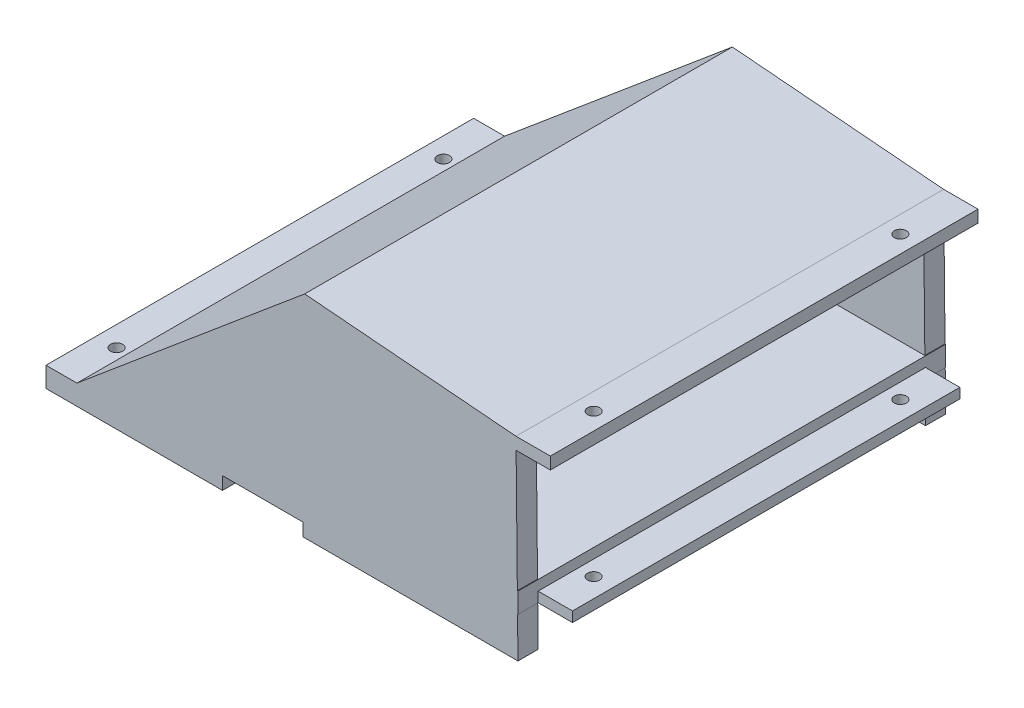
SolidWorks part; units mm, degrees
ref_plane "Front Plane" through (0, 0, 0) normal (0, 0, 1) x (1, 0, 0)
ref_plane "Top Plane" through (0, 0, 0) normal (0, 1, 0) x (1, 0, 0)
ref_plane "Right Plane" through (0, 0, 0) normal (1, 0, 0) x (0, 0, -1)
sketch "Sketch1" plane through (0, 0, 0) normal (0, 0, 1) x (1, 0, 0)
  line L2 (0, 0) -> (0, -6)
  line L6 (-234.6631, -86) -> (-250, -86)
  line L7 (-250, -86) -> (-250, -96)
  line L8 (-250, -96) -> (-230, -96)
  line L12 (-206.1649, -76) -> (0.9775, -76)
  line L16 (-16.0425, -66) -> (-118.6219, -66)
  line L20 (-16.0425, -66) -> (-16.0425, -71)
  line L21 (-16.0425, -71) -> (0.9775, -71)
  line L22 (0.9775, -71) -> (0.9775, -76)
  line L26 (0.9775, -66) -> (-92.0225, -66) construction
  line L27 (0.9775, -66) -> (0.9775, -13.5) construction
  line L28 (0.9775, -13.5) -> (-92.0225, -13.5) construction
  line L29 (-92.0225, -66) -> (-92.0225, -13.5) construction
  line L30 (-17.02, -6) -> (-118.6219, 2.463)
  line L31 (-118.6219, -1) -> (-99.8219, -1) construction
  line L32 (-118.6219, -1) -> (-118.6219, -66) construction
  line L33 (-118.6219, -66) -> (-99.8219, -66) construction
  line L34 (-99.8219, -1) -> (-99.8219, -66) construction
  line L39 (-17.02, -6) -> (0, -6)
  line L41 (-118.6219, 2.463) -> (-118.6219, -66)
  line L44 (-138.6219, -19.3246) -> (-138.6219, -66)
  line L45 (-138.6219, -66) -> (-194.2474, -66)
  line L46 (0, 0) -> (-17.02, 0)
  line L48 (-230, -96) -> (-206.1649, -76)
  line L49 (-17.02, 0) -> (-121.7736, 8.7256)
  line L50 (-234.6631, -86) -> (-121.7736, 8.7256)
  line L51 (-194.2474, -66) -> (-138.6219, -19.3246)
  point P13 (-250, -91)
  point P18 (0, -3)
  dimension "D1" = 250
  dimension "D2" = 20
  dimension "D3" = 20
  dimension "D4" = 10
  dimension "D5" = 5
  dimension "D6" = 6
  dimension "D7" = 20
  dimension "D8" = 5
  dimension "D9" = 65
  dimension "D10" = 52.5
  dimension "D11" = 40
  dimension "D12" = 93
  dimension "D13" = 18.8
  dimension "D14" = 65
  dimension "D18" = 17.02
extrude "Boss-Extrude1" add sketch "Sketch1" along normal blind 212
sketch "Sketch2" plane through (0, -76, 0) normal (0, -1, 0) x (1, 0, 0)
  line L1 (0.9775, 212) -> (-16.0425, 212)
  line L2 (0.9775, 212) -> (0.9775, 202)
  line L3 (0.9775, 202) -> (-16.0425, 202)
  line L4 (-16.0425, 212) -> (-16.0425, 202)
  line L5 (0.9775, 0) -> (-16.0425, 0)
  line L6 (0.9775, 0) -> (0.9775, 10)
  line L7 (0.9775, 10) -> (-16.0425, 10)
  line L8 (-16.0425, 0) -> (-16.0425, 10)
  dimension "D1" = 10
  dimension "D2" = 17.02
extrude "Cut-Extrude1" cut sketch "Sketch2" against normal up to next
sketch "Sketch3" plane through (-118.6219, 0, 0) normal (1, 0, 0) x (0, 0, -1)
  line L1 (-163.5, -0.037) -> (-48.5, -0.037) construction
  line L2 (-163.5, -0.037) -> (-163.5, -65.037) construction
  line L3 (-163.5, -65.037) -> (-48.5, -65.037) construction
  line L4 (-48.5, -0.037) -> (-48.5, -65.037) construction
  line L6 (-212, 2.463) -> (0, 2.463) construction
  line L7 (-212, -66) -> (-212, 2.463) construction
  line L8 (-106, -65.037) -> (-106, -6) construction
  circle A0 centre (-159.5, -12.537) radius 1.5
  circle A1 centre (-159.5, -52.537) radius 1.5
  circle A2 centre (-52.5, -52.537) radius 1.5
  circle A3 centre (-52.5, -12.537) radius 1.5
  dimension "D1" = 3
  dimension "D2" = 3
  dimension "D7" = 4
  dimension "D3" = 115
  dimension "D4" = 65
  dimension "D5" = 2.5
  dimension "D6" = 48.5
  dimension "D8" = 12.5
  dimension "D9" = 12.5
extrude "Cut-Extrude2" cut sketch "Sketch3" against normal blind 15
sketch "Sketch4" plane through (0, -86, 0) normal (0, 1, 0) x (1, 0, 0)
  line L0 (-250, -106) -> (-234.6631, -106) construction
  line L1 (-250, -212) -> (-250, 0) construction
  line L2 (-234.6631, -212) -> (-234.6631, 0) construction
  line L3 (-234.6631, 0) -> (-250, 0) construction
  circle A0 centre (-240, -25) radius 3
  circle A1 centre (-240, -187) radius 3
  dimension "D1" = 6
  dimension "D2" = 25
  dimension "D3" = 10
extrude "Cut-Extrude3" cut sketch "Sketch4" against normal blind 15
sketch "Sketch5" plane through (0, -66, 0) normal (0, 1, 0) x (1, 0, 0)
  line L0 (-118.6219, -212) -> (-118.6219, 0) construction
  line L1 (-113.6219, -176.8118) -> (-83.6219, -176.8118)
  line L2 (-113.6219, -176.8118) -> (-113.6219, -191.8118)
  line L3 (-113.6219, -191.8118) -> (-83.6219, -191.8118)
  line L4 (-83.6219, -176.8118) -> (-83.6219, -191.8118)
  dimension "D1" = 15
  dimension "D2" = 5
  dimension "D3" = 30
extrude "Cut-Extrude4" cut sketch "Sketch5" against normal blind 15
sketch "Sketch6" plane through (0, 0, 0) normal (0, 1, 0) x (1, 0, 0)
  line L0 (0, 0) -> (-17.02, 0) construction
  line L1 (-17.02, -212) -> (-17.02, 0) construction
  line L2 (-17.02, -106) -> (0.9775, -106) construction
  line L3 (0.9775, -202) -> (0.9775, -10) construction
  circle A0 centre (-8.52, -30) radius 3
  circle A1 centre (-8.52, -182) radius 3
  dimension "D1" = 6
  dimension "D2" = 30
  dimension "D3" = 8.5
extrude "Cut-Extrude5" cut sketch "Sketch6" against normal through all both and the other way through all
sketch "Sketch7" plane through (0, 0, 212) normal (0, 0, 1) x (1, 0, 0)
  line L10 (-17.02, 0) -> (-121.7736, 8.7256) construction
  line L11 (-17.02, 0) -> (-121.7736, 8.7256)
  line L13 (-250, -86) -> (-250, -96) construction
  line L14 (-234.6631, -86) -> (-250, -86) construction
  line L15 (-121.7736, 8.7256) -> (-234.6631, -86) construction
  line L16 (-250, -86) -> (-250, -96)
  line L17 (-234.6631, -86) -> (-250, -86)
  line L18 (-121.7736, 8.7256) -> (-234.6631, -86)
  line L19 (-250, -96) -> (-16.0425, -96)
  line L20 (-16.0425, -96) -> (-17.02, 0)
extrude "Boss-Extrude2" add sketch "Sketch7" against normal blind 10
sketch "Sketch8" plane through (0, 0, 0) normal (0, 0, -1) x (-1, 0, 0)
  line L0 (250, -96) -> (230, -96) construction
  line L1 (250, -86) -> (250, -96) construction
  line L2 (234.6631, -86) -> (250, -86) construction
  line L3 (121.7736, 8.7256) -> (234.6631, -86) construction
  line L4 (17.02, 0) -> (121.7736, 8.7256) construction
  line L5 (250, -96) -> (230, -96)
  line L6 (250, -86) -> (250, -96)
  line L7 (234.6631, -86) -> (250, -86)
  line L8 (121.7736, 8.7256) -> (234.6631, -86)
  line L9 (17.02, 0) -> (121.7736, 8.7256)
  line L10 (230, -96) -> (16.0425, -96)
  line L11 (16.0425, -96) -> (17.02, 0)
extrude "Boss-Extrude3" add sketch "Sketch8" against normal blind 10
sketch "Sketch9" plane through (0, 0, 212) normal (0, 0, 1) x (1, 0, 0)
  line L0 (-250, -96) -> (-16.0425, -96) construction
  line L1 (-162.5, -96) -> (-122.5, -96)
  line L2 (-162.5, -96) -> (-162.5, -89.65)
  line L3 (-162.5, -89.65) -> (-122.5, -89.65)
  line L4 (-122.5, -96) -> (-122.5, -89.65)
  line L5 (-250, -86) -> (-250, -96) construction
  dimension "D1" = 87.5
  dimension "D2" = 40
  dimension "D3" = 6.35
extrude "Cut-Extrude6" cut sketch "Sketch9" against normal through all both
